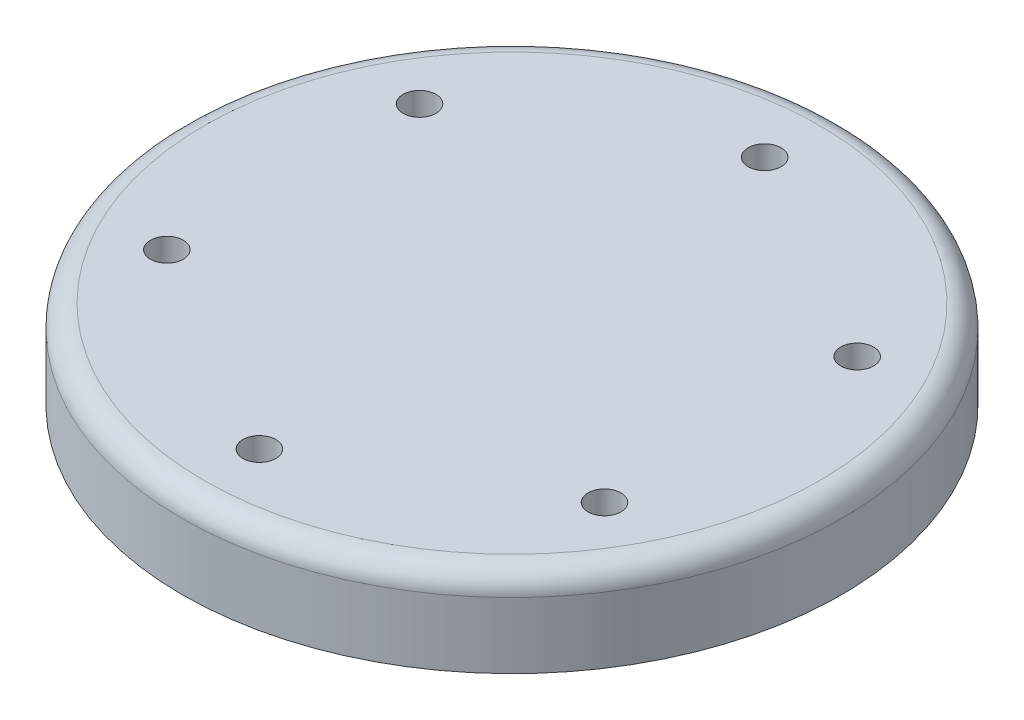
SolidWorks part; units mm, degrees
ref_plane "Front Plane" through (0, 0, 0) normal (0, 0, 1) x (1, 0, 0)
ref_plane "Top Plane" through (0, 0, 0) normal (0, 1, 0) x (1, 0, 0)
ref_plane "Right Plane" through (0, 0, 0) normal (1, 0, 0) x (0, 0, -1)
sketch "Sketch1" plane through (0, 0, 0) normal (0, 1, 0) x (1, 0, 0)
  circle A0 centre (0, 0) radius 30
  circle A1 centre (0, 0) radius 23 construction
  circle A2 centre (0, 23) radius 1.5
  circle A3 centre (19.9191, 11.5009) radius 1.5
  circle A4 centre (19.9201, -11.4991) radius 1.5
  circle A5 centre (0.002, -23) radius 1.5
  circle A6 centre (-19.9171, -11.5009) radius 1.5
  circle A7 centre (-19.9181, 11.4991) radius 1.5
  point P18 (0.001, 0)
  dimension "D1" = 60
  dimension "D2" = 46
  dimension "D3" = 3
  dimension "D4" = 6
extrude "Boss-Extrude1" add sketch "Sketch1" along normal blind 8
fillet "Fillet1" radius 2 1 edges at (0, 8, 30)
